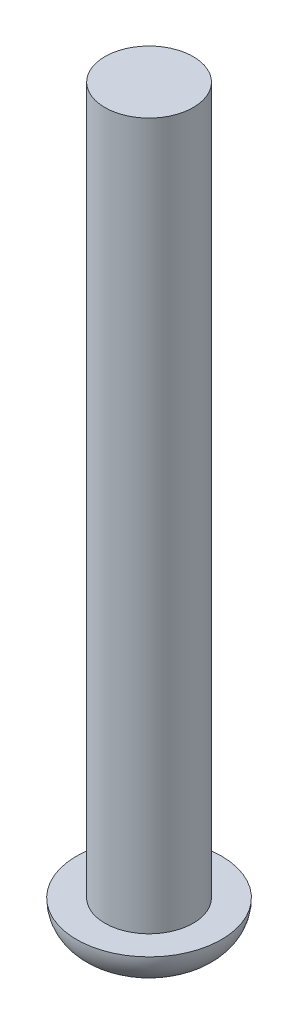
SolidWorks part; units mm, degrees
ref_plane "Front Plane" through (0, 0, 0) normal (0, 0, 1) x (1, 0, 0)
ref_plane "Top Plane" through (0, 0, 0) normal (0, 1, 0) x (1, 0, 0)
ref_plane "Right Plane" through (0, 0, 0) normal (1, 0, 0) x (0, 0, -1)
sketch "Sketch1" plane through (0, 0, 0) normal (0, 1, 0) x (1, 0, 0)
  circle A0 centre (0, 0) radius 2.5
  dimension "D1" = 5
extrude "Boss-Extrude1" add sketch "Sketch1" along normal blind 40 contours A0
sketch "Sketch2" plane through (0, 0, 0) normal (0, -1, 0) x (1, 0, 0)
  circle A0 centre (0, 0) radius 4.1
  circle A1 centre (0, 0) radius 2.5 construction
  circle A2 centre (0, 0) radius 2.5 construction
  dimension "D1" = 8.2
extrude "Boss-Extrude2" add sketch "Sketch2" along normal blind 2
fillet "Fillet1" radius 2 1 edges at (0, -2, -4.1)
sketch "Sketch3" plane through (0, -2, 0) normal (0, -1, 0) x (1, 0, 0)
  line L0 (0.375, 0.375) -> (1.5, 0.375)
  line L1 (-0.375, -1.5) -> (0.375, -1.5)
  line L2 (-0.375, -1.5) -> (-0.375, -0.375)
  line L3 (-0.375, 1.5) -> (0.375, 1.5)
  line L4 (0.375, -1.5) -> (0.375, -0.375)
  line L7 (-1.5, -0.375) -> (-0.375, -0.375)
  line L8 (-1.5, -0.375) -> (-1.5, 0.375)
  line L9 (-1.5, 0.375) -> (-0.375, 0.375)
  line L10 (1.5, -0.375) -> (1.5, 0.375)
  line L15 (0.375, 0.375) -> (0.375, 1.5)
  line L16 (0.375, -0.375) -> (1.5, -0.375)
  line L17 (-0.375, 0.375) -> (-0.375, 1.5)
  point P0 (0, 0)
  point P6 (0, 0)
  dimension "D1" = 3
  dimension "D2" = 0.75
extrude "Cut-Extrude1" cut sketch "Sketch3" against normal blind 1 draft 15
sketch "Sketch5" plane through (0, 0, 0) normal (0, 0, 1) x (1, 0, 0)
  line L0 (-2.1, -2) -> (2.1, -2) construction
  line L3 (0, 0) -> (0, 24) construction
  point P6 (0, 11)
  dimension "D1" = 13
  dimension "D2" = 26
sketch "Sketch6" [suppressed] plane through (0, 0, 0) normal (0, 0, 1) x (1, 0, 0)
  line L0 (0, 0) -> (0, 70) construction
  line L1 (4, 70) -> (-4, 70) construction
